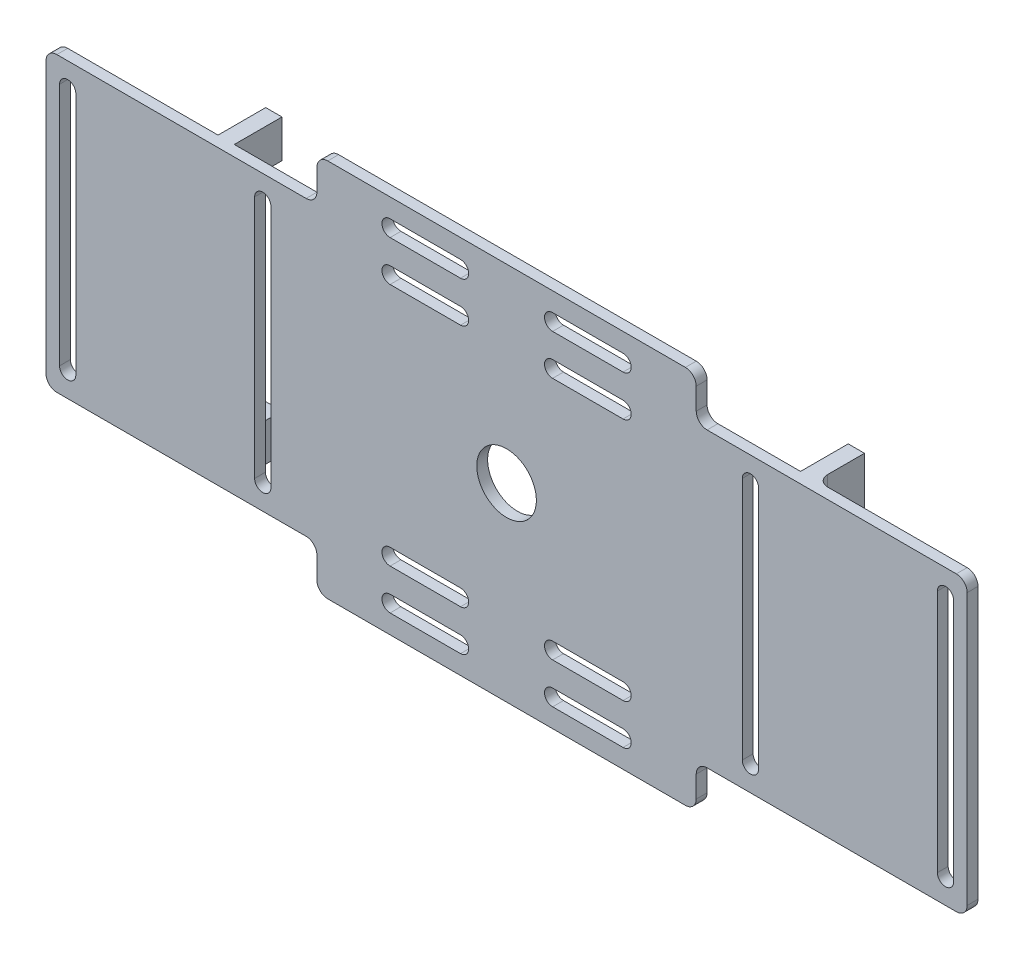
SolidWorks part; units mm, degrees
ref_plane "前基準面" through (0, 0, 0) normal (0, 0, 1) x (1, 0, 0)
ref_plane "上基準面" through (0, 0, 0) normal (0, 1, 0) x (1, 0, 0)
ref_plane "右基準面" through (0, 0, 0) normal (1, 0, 0) x (0, 0, -1)
sketch "草圖1" plane through (0, 0, 0) normal (0, 0, 1) x (1, 0, 0)
  line L1 (-85, 35) -> (85, 35)
  line L2 (-85, 35) -> (-85, -35)
  line L3 (-85, -35) -> (85, -35)
  line L4 (85, 35) -> (85, -35)
  line L5 (-85, 35) -> (85, -35) construction
  line L6 (-85, -35) -> (85, 35) construction
  point P0 (0, 0)
  dimension "D1" = 170
  dimension "D2" = 70
extrude "填料-伸長1" add sketch "草圖1" along normal blind 2
sketch "草圖2" plane through (0, 0, 2) normal (0, 0, 1) x (1, 0, 0)
  line L0 (-1000, 0) -> (49000, 0) construction
  line L1 (45, -986.1952) -> (45, 49013.8048) construction
  line L2 (-81, -962.7943) -> (-81, 49037.2057) construction
  line L3 (45, -22.5) -> (45, 22.5) construction
  line L4 (43.5, -22.5) -> (43.5, 22.5)
  line L5 (46.5, -22.5) -> (46.5, 22.5)
  line L6 (-45, -1000) -> (-45, 49000) construction
  line L7 (-45, -22.5) -> (-45, 22.5) construction
  line L8 (-46.5, -22.5) -> (-46.5, 22.5)
  line L9 (-43.5, -22.5) -> (-43.5, 22.5)
  line L10 (0, -1000) -> (0, 49000) construction
  line L11 (-1005.6924, 30) -> (48994.3076, 30) construction
  line L12 (-1002.3566, -30) -> (48997.6434, -30) construction
  line L13 (21.5, 30) -> (8.5, 30) construction
  line L16 (21.5, 28.5) -> (8.5, 28.5)
  line L19 (81, -968.4295) -> (81, 49031.5705) construction
  line L20 (-81, -22.5) -> (-81, 22.5) construction
  line L21 (-82.5, -22.5) -> (-82.5, 22.5)
  line L22 (-79.5, -22.5) -> (-79.5, 22.5)
  line L23 (81, -22.5) -> (81, 22.5) construction
  line L24 (79.5, -22.5) -> (79.5, 22.5)
  line L25 (82.5, -22.5) -> (82.5, 22.5)
  line L26 (21.5, 31.5) -> (8.5, 31.5)
  line L27 (21.5, 22.5) -> (8.5, 22.5) construction
  line L28 (21.5, 21) -> (8.5, 21)
  line L29 (21.5, 24) -> (8.5, 24)
  line L30 (-21.5, 30) -> (-8.5, 30) construction
  line L31 (-21.5, 28.5) -> (-8.5, 28.5)
  line L32 (-21.5, 31.5) -> (-8.5, 31.5)
  line L33 (-21.5, 22.5) -> (-8.5, 22.5) construction
  line L34 (-21.5, 21) -> (-8.5, 21)
  line L35 (-21.5, 24) -> (-8.5, 24)
  line L36 (21.5, -30) -> (8.5, -30) construction
  line L37 (21.5, -28.5) -> (8.5, -28.5)
  line L38 (21.5, -31.5) -> (8.5, -31.5)
  line L39 (21.5, -22.5) -> (8.5, -22.5) construction
  line L40 (21.5, -21) -> (8.5, -21)
  line L41 (21.5, -24) -> (8.5, -24)
  line L42 (-21.5, -30) -> (-8.5, -30) construction
  line L43 (-21.5, -28.5) -> (-8.5, -28.5)
  line L44 (-21.5, -31.5) -> (-8.5, -31.5)
  line L45 (-21.5, -22.5) -> (-8.5, -22.5) construction
  line L46 (-21.5, -21) -> (-8.5, -21)
  line L47 (-21.5, -24) -> (-8.5, -24)
  arc A0 (43.5, -22.5) -> (46.5, -22.5) centre (45, -22.5) ccw
  arc A1 (46.5, 22.5) -> (43.5, 22.5) centre (45, 22.5) ccw
  arc A2 (-46.5, -22.5) -> (-43.5, -22.5) centre (-45, -22.5) ccw
  arc A3 (-43.5, 22.5) -> (-46.5, 22.5) centre (-45, 22.5) ccw
  arc A12 (-82.5, -22.5) -> (-79.5, -22.5) centre (-81, -22.5) ccw
  arc A13 (-79.5, 22.5) -> (-82.5, 22.5) centre (-81, 22.5) ccw
  arc A14 (79.5, -22.5) -> (82.5, -22.5) centre (81, -22.5) ccw
  arc A15 (82.5, 22.5) -> (79.5, 22.5) centre (81, 22.5) ccw
  circle A16 centre (0, 0) radius 5.5
  arc A17 (21.5, 28.5) -> (21.5, 31.5) centre (21.5, 30) ccw
  arc A18 (8.5, 31.5) -> (8.5, 28.5) centre (8.5, 30) ccw
  arc A19 (21.5, 21) -> (21.5, 24) centre (21.5, 22.5) ccw
  arc A20 (8.5, 24) -> (8.5, 21) centre (8.5, 22.5) ccw
  arc A21 (-21.5, 28.5) -> (-21.5, 31.5) centre (-21.5, 30) cw
  arc A22 (-8.5, 31.5) -> (-8.5, 28.5) centre (-8.5, 30) cw
  arc A23 (-21.5, 21) -> (-21.5, 24) centre (-21.5, 22.5) cw
  arc A24 (-8.5, 24) -> (-8.5, 21) centre (-8.5, 22.5) cw
  arc A25 (21.5, -28.5) -> (21.5, -31.5) centre (21.5, -30) cw
  arc A26 (8.5, -31.5) -> (8.5, -28.5) centre (8.5, -30) cw
  arc A27 (21.5, -21) -> (21.5, -24) centre (21.5, -22.5) cw
  arc A28 (8.5, -24) -> (8.5, -21) centre (8.5, -22.5) cw
  arc A29 (-21.5, -28.5) -> (-21.5, -31.5) centre (-21.5, -30) ccw
  arc A30 (-8.5, -31.5) -> (-8.5, -28.5) centre (-8.5, -30) ccw
  arc A31 (-21.5, -21) -> (-21.5, -24) centre (-21.5, -22.5) ccw
  arc A32 (-8.5, -24) -> (-8.5, -21) centre (-8.5, -22.5) ccw
  point P9 (45, 0)
  point P16 (-45, 0)
  point P31 (15, 30)
  point P39 (15, 22.5)
  point P47 (-81, 0)
  point P54 (81, 0)
  point P63 (-15, 30)
  point P70 (-15, 22.5)
  point P77 (15, -30)
  point P84 (15, -22.5)
  point P91 (-15, -30)
  point P98 (-15, -22.5)
  dimension "D10" = 1.5
  dimension "D20" = 11
  dimension "D12" = 8.5
  dimension "D2" = 45
  dimension "D3" = 3
  dimension "D4" = 90
  dimension "D5" = 45
  dimension "D6" = 3
  dimension "D7" = 45
  dimension "D8" = 60
  dimension "D9" = 30
  dimension "D11" = 13
  dimension "D13" = 2
  dimension "D14" = 162
  dimension "D15" = 81
  dimension "D16" = 3
  dimension "D17" = 45
  dimension "D18" = 45
  dimension "D19" = 3
extrude "除料-伸長1" cut sketch "草圖2" against normal through all
sketch "草圖4" plane through (0, 0, 2) normal (0, 0, 1) x (1, 0, 0)
  line L0 (0, 52.0279) -> (0, -54.8062) construction
  line L1 (85, 35) -> (33, 35)
  line L2 (85, 35) -> (85, 25)
  line L3 (83, 27) -> (37, 27)
  line L4 (35, 33) -> (35, 29)
  line L5 (85, -35) -> (85, 35) construction
  line L6 (-98.2871, 0) -> (106.0141, 0) construction
  line L8 (35, -33) -> (35, -29)
  line L9 (83, -27) -> (37, -27)
  line L10 (85, -35) -> (85, -25)
  line L11 (85, -35) -> (33, -35)
  line L12 (-85, -35) -> (-33, -35)
  line L13 (-85, -35) -> (-85, -25)
  line L14 (-83, -27) -> (-37, -27)
  line L15 (-35, -33) -> (-35, -29)
  line L16 (-35, 33) -> (-35, 29)
  line L17 (-83, 27) -> (-37, 27)
  line L18 (-85, 35) -> (-85, 25)
  line L19 (-85, 35) -> (-33, 35)
  arc A0 (83, 27) -> (85, 25) centre (83, 25) cw
  arc A1 (37, 27) -> (35, 29) centre (37, 29) cw
  arc A2 (35, 33) -> (33, 35) centre (33, 33) ccw
  arc A3 (35, -33) -> (33, -35) centre (33, -33) cw
  arc A4 (37, -27) -> (35, -29) centre (37, -29) ccw
  arc A5 (83, -27) -> (85, -25) centre (83, -25) ccw
  arc A6 (-83, -27) -> (-85, -25) centre (-83, -25) cw
  arc A7 (-37, -27) -> (-35, -29) centre (-37, -29) cw
  arc A8 (-35, -33) -> (-33, -35) centre (-33, -33) ccw
  arc A9 (-35, 33) -> (-33, 35) centre (-33, 33) cw
  arc A10 (-37, 27) -> (-35, 29) centre (-37, 29) ccw
  arc A11 (-83, 27) -> (-85, 25) centre (-83, 25) ccw
  dimension "D1" = 2
  dimension "D2" = 2
  dimension "D3" = 2
  dimension "D4" = 52
  dimension "D5" = 8
extrude "除料-伸長2" cut sketch "草圖4" against normal through all
sketch "草圖5" plane through (0, 0, 2) normal (0, 0, 1) x (1, 0, 0)
  line L0 (-83, 27) -> (-37, 27) construction
  line L1 (-55.25, 27) -> (-52.25, 27)
  line L2 (-55.25, 27) -> (-55.25, -27)
  line L3 (-55.25, -27) -> (-52.25, -27)
  line L4 (-52.25, 27) -> (-52.25, -27)
  line L5 (-37, -27) -> (-83, -27) construction
  line L6 (0, 48.2539) -> (0, -45.9001) construction
  line L7 (52.25, 27) -> (52.25, -27)
  line L8 (55.25, -27) -> (52.25, -27)
  line L9 (55.25, 27) -> (55.25, -27)
  line L10 (55.25, 27) -> (52.25, 27)
  dimension "D1" = 3
  dimension "D2" = 52.25
extrude "填料-伸長2" add sketch "草圖5" against normal blind 10.8 contours L2 L3 L4 L1 | L7 L8 L9 L10
fillet "圓角1" radius 2 1 edges at (55.25, 0, 0)
sketch "草圖6" plane through (0, 0, -8.8) normal (0, 0, -1) x (-1, 0, 0)
  line L0 (-19.1896, 0) -> (94.9262, 0) construction
  line L1 (55.25, 27) -> (55.25, -27) construction
  line L2 (52.25, -20) -> (55.25, -20)
  line L3 (52.25, -20) -> (52.25, 20)
  line L4 (52.25, 20) -> (55.25, 20)
  line L5 (55.25, -20) -> (55.25, 20)
  line L6 (52.25, -20) -> (55.25, 20) construction
  line L7 (52.25, 20) -> (55.25, -20) construction
  line L8 (52.25, 27) -> (52.25, -27) construction
  point P2 (53.75, 0)
  dimension "D1" = 40
extrude "除料-伸長3" cut sketch "草圖6" against normal blind 6
fillet "圓角2" radius 2 2 edges at (-53.75, -20, -2.8) (-53.75, 20, -2.8)
